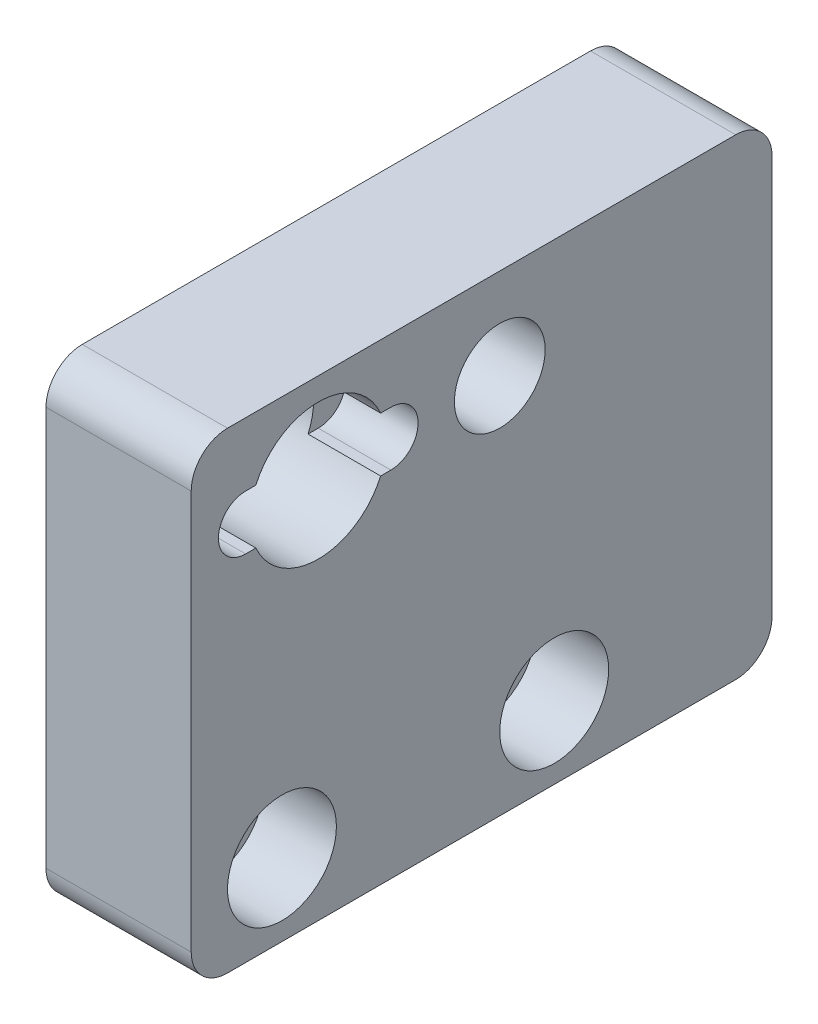
SolidWorks part; units mm, degrees
material "6061 Alloy"
ref_plane "Front Plane" through (0, 0, 0) normal (0, 0, 1) x (1, 0, 0)
ref_plane "Top Plane" through (0, 0, 0) normal (0, 1, 0) x (1, 0, 0)
ref_plane "Right Plane" through (0, 0, 0) normal (1, 0, 0) x (0, 0, -1)
sketch "Sketch1" plane through (0, 0, 0) normal (1, 0, 0) x (0, 0, -1)
  line L1 (0, 0) -> (32, 0)
  line L2 (0, 0) -> (0, 26)
  line L3 (0, 26) -> (32, 26)
  line L4 (32, 0) -> (32, 26)
  dimension "D1" = 32
  dimension "D2" = 26
extrude "Boss-Extrude1" add sketch "Sketch1" along normal blind 8
sketch "Sketch2" plane through (8, 0, 0) normal (1, 0, 0) x (0, 0, -1)
  line L0 (0, 0) -> (32, 0) construction
  line L1 (0, 26) -> (0, 0) construction
  circle A2 centre (20, 4) radius 1.6
  circle A3 centre (20, 4) radius 3
  circle A4 centre (5, 4) radius 1.6
  circle A5 centre (5, 4) radius 3
  dimension "D3" = 20
  dimension "D4" = 6
  dimension "D9" = 6
  dimension "D10" = 3.2
  dimension "D2" = 4
  dimension "D11" = 5
extrude "Cut-Extrude1" cut sketch "Sketch2" against normal blind 4 contours A3 | A5
extrude "Cut-Extrude2" cut sketch "Sketch2<3>" against normal blind 8 contours A2 | A4
sketch "Sketch2<3>" plane through (8, 0, 0) normal (1, 0, 0) x (0, 0, -1) same geometry as "Sketch2"
fillet "Fillet1" radius 2 4 edges at (4, 0, 0) (4, 0, -32) (4, 26, -32) (4, 26, 0)
sketch "Sketch3" plane through (8, 0, 0) normal (1, 0, 0) x (0, 0, -1)
  line L0 (30, 26) -> (2, 26) construction
  line L1 (32, 2) -> (32, 24) construction
  circle A0 centre (17, 21) radius 2.5
  dimension "D2" = 15
  dimension "D3" = 5
  dimension "D1" = 5
extrude "Cut-Extrude3" cut sketch "Sketch3" against normal blind 8
sketch "Sketch4" plane through (8, 0, 0) normal (1, 0, 0) x (0, 0, -1)
  line L0 (30, 26) -> (2, 26) construction
  line L1 (32, 2) -> (32, 24) construction
  line L2 (3, 21) -> (11, 21) construction
  line L3 (3, 22.5) -> (11, 22.5)
  line L4 (3, 19.5) -> (11, 19.5)
  circle A0 centre (7, 21) radius 3.75
  arc A1 (3, 22.5) -> (3, 19.5) centre (3, 21) ccw
  arc A2 (11, 19.5) -> (11, 22.5) centre (11, 21) ccw
  point P8 (7, 21)
  dimension "D3" = 7.5
  dimension "D4" = 1.5
  dimension "D1" = 5
  dimension "D2" = 25
  dimension "D5" = 4
extrude "Cut-Extrude4" cut sketch "Sketch4" against normal blind 8 contours A0
extrude "Cut-Extrude5" cut sketch "Sketch4<3>" against normal blind 4 contours L3 A2 L4 A1
sketch "Sketch4<3>" plane through (8, 0, 0) normal (1, 0, 0) x (0, 0, -1) same geometry as "Sketch4"
ref_plane "Plane7" through (0, 0, -17) normal (0, 0, 1) x (1, 0, 0)
sketch "Sketch6" plane through (0, 0, -17) normal (0, 0, 1) x (1, 0, 0)
  line L0 (-2.1245, 21) -> (11.3558, 21) construction
  line L1 (8, 26) -> (0, 26) construction
  dimension "D1" = 5
hole_wizard "Ø2.0mm Dowel Hole1" positions "Sketch13" profile "Sketch14" hole size "Ø2.0" standard "ANSI Metric"
sketch "Sketch13" plane through (0, 0, -32) normal (0, 0, -1) x (-1, 0, 0)
  line L1 (0, 0) -> (-8, 0) construction
  line L2 (-8, 2) -> (-8, 24) construction
  point P0 (-6, 3)
  dimension "D1" = 2
  dimension "D2" = 3
sketch "Sketch14" plane through (6, 3, -32) normal (1, 0, 0) x (0, 1, 0)
  line L0 (0, 0) -> (0, 6.6009)
  line L1 (0, 6.6009) -> (1, 6)
  line L2 (1, 6) -> (1, 0)
  line L5 (1, 0) -> (0, 0)
  line L10 (0, 6.6009) -> (-1, 6) construction
  line L11 (0, -6.35) -> (0, 107.95) construction
  dimension "Hole Dia." = 2
  dimension "Hole Depth" = 6
  dimension "Drill Angle" = 118
sketch "Sketch15" plane through (0, 0, 0) normal (-1, 0, 0) x (0, 0, 1)
  line L0 (-2, 0) -> (-30, 0) construction
  line L1 (-15, 4) -> (-10, 4)
  line L2 (-15, 3) -> (-15, 0)
  line L3 (-15, 0) -> (-10, 0)
  line L4 (-10, 3) -> (-10, 0)
  circle A0 centre (-20, 4) radius 1.6 construction
  arc A1 (-15, 4) -> (-15, 3) centre (-15, 3.5) ccw
  arc A2 (-10, 3) -> (-10, 4) centre (-10, 3.5) ccw
  dimension "D3" = 5
  dimension "D4" = 1
  dimension "D1" = 5
  dimension "D2" = 4
extrude "Cut-Extrude6" cut sketch "Sketch15" against normal blind 4
